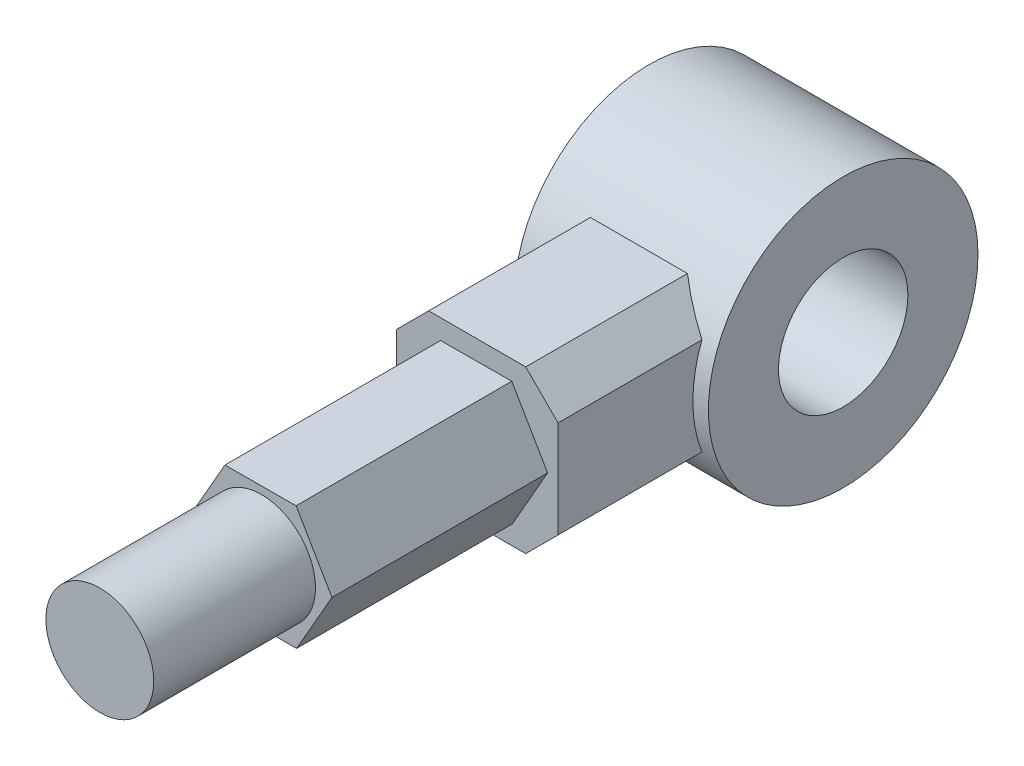
SolidWorks part; units mm, degrees
ref_plane "Front Plane" through (0, 0, 0) normal (0, 0, 1) x (1, 0, 0)
ref_plane "Top Plane" through (0, 0, 0) normal (0, 1, 0) x (1, 0, 0)
ref_plane "Right Plane" through (0, 0, 0) normal (1, 0, 0) x (0, 0, -1)
sketch "Sketch1" plane through (0, 0, 0) normal (1, 0, 0) x (0, 0, -1)
  circle A0 centre (0, 0) radius 12.5
  circle A1 centre (0, 0) radius 6
  dimension "D1" = 25
  dimension "D2" = 12
extrude "Boss-Extrude1" add sketch "Sketch1" along normal blind 18
sketch "Sketch2" plane through (0, 0, 0) normal (0, 0, 1) x (1, 0, 0)
  line L1 (1.5601, 7.5) -> (16.5601, 7.5)
  line L2 (1.5601, 7.5) -> (1.5601, -7.5)
  line L3 (1.5601, -7.5) -> (16.5601, -7.5)
  line L4 (16.5601, 7.5) -> (16.5601, -7.5)
  dimension "D1" = 15
  dimension "D2" = 7.5
  dimension "D3" = 15
extrude "Boss-Extrude2" add sketch "Sketch2" along normal blind 25
sketch "Sketch3" plane through (0, 0, 25) normal (0, 0, 1) x (1, 0, 0)
  line L1 (12.2661, 5.7004) -> (5.6669, 5.671)
  line L2 (5.6669, 5.671) -> (2.3927, -0.0588)
  line L3 (2.3927, -0.0588) -> (5.7177, -5.7592)
  line L4 (5.7177, -5.7592) -> (12.317, -5.7298)
  line L5 (12.317, -5.7298) -> (15.5912, 0)
  line L6 (15.5912, 0) -> (12.2661, 5.7004)
  circle A0 centre (8.9919, -0.0294) radius 5.7152 construction
  point P1 (8.9919, -0.0588)
extrude "Boss-Extrude3" add sketch "Sketch3" along normal blind 20 contours L6 L1 L2 L3 L4 L5
chamfer "Chamfer1" distance 3 angle 45 4 edges at (1.5601, -7.5, 17.5) (16.5601, -7.5, 17.5) (1.5601, 7.5, 17.5) (16.5601, 7.5, 17.5)
sketch "Sketch4" plane through (0, 0, 45) normal (0, 0, 1) x (1, 0, 0)
  circle A0 centre (9.0667, 0) radius 5
  point P2 (9.0667, 0)
  dimension "D1" = 10
extrude "Boss-Extrude4" add sketch "Sketch4" along normal blind 15
extrude "Cut-Extrude2" cut sketch "Sketch1<3>" against normal through all and the other way through all contours A1
sketch "Sketch1<3>" plane through (0, 0, 0) normal (1, 0, 0) x (0, 0, -1) same geometry as "Sketch1"
